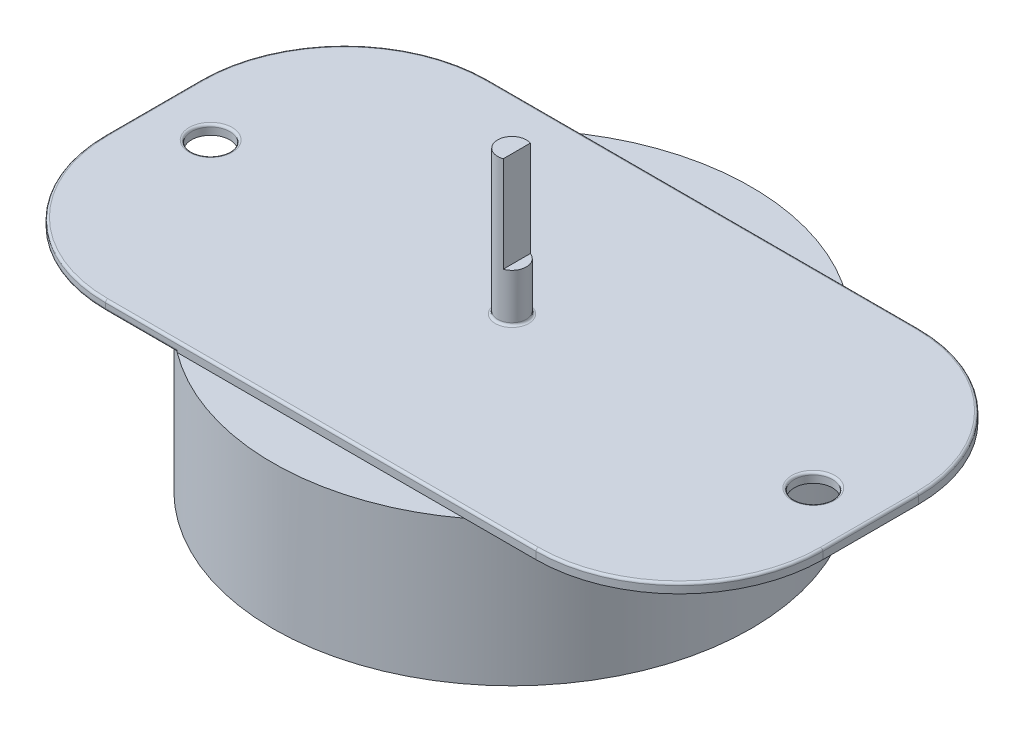
SolidWorks part; units mm, degrees
ref_plane "Plano frontal" through (0, 0, 0) normal (0, 0, 1) x (1, 0, 0)
ref_plane "Plano superior" through (0, 0, 0) normal (0, 1, 0) x (1, 0, 0)
ref_plane "Plano direito" through (0, 0, 0) normal (1, 0, 0) x (0, 0, -1)
sketch "Esboço1" plane through (0, 0, 0) normal (0, 1, 0) x (1, 0, 0)
  circle A0 centre (0, 0) radius 50
extrude "Ressalto-extrusão1" add sketch "Esboço1" along normal blind 30
sketch "Esboço2" plane through (0, 30, 0) normal (0, 1, 0) x (1, 0, 0)
  line L1 (-45, -40) -> (45, -40)
  line L2 (-75, -10) -> (-75, 10)
  line L3 (-45, 40) -> (45, 40)
  line L4 (75, -10) -> (75, 10)
  line L5 (-75, -40) -> (75, 40) construction
  line L6 (-75, 40) -> (75, -40) construction
  arc A0 (45, 40) -> (75, 10) centre (45, 10) cw
  arc A1 (45, -40) -> (75, -10) centre (45, -10) ccw
  arc A2 (-45, -40) -> (-75, -10) centre (-45, -10) cw
  arc A3 (-75, 10) -> (-45, 40) centre (-45, 10) cw
  point P0 (0, 0)
  dimension "D3" = 30
  dimension "D1" = 150
  dimension "D2" = 80
extrude "Ressalto-extrusão2" add sketch "Esboço2" along normal blind 2
sketch "Esboço3" plane through (0, 32, 0) normal (0, 1, 0) x (1, 0, 0)
  circle A0 centre (0, 0) radius 3
  dimension "D1" = 6
extrude "Ressalto-extrusão3" add sketch "Esboço3" along normal blind 30
sketch "Esboço4" plane through (0, 62, 0) normal (0, 1, 0) x (1, 0, 0)
  line L1 (1, -3.3934) -> (3.9135, -3.3934)
  line L2 (1, -3.3934) -> (1, 3.3718)
  line L3 (1, 3.3718) -> (3.9135, 3.3718)
  line L4 (3.9135, -3.3934) -> (3.9135, 3.3718)
  dimension "D1" = 1
extrude "Corte-extrusão1" cut sketch "Esboço4" against normal blind 20
sketch "Esboço6" plane through (0, 32, 0) normal (0, 1, 0) x (1, 0, 0)
  line L0 (-75, 10) -> (-75, -10) construction
  line L1 (0, -17.6) -> (0, 17.6) construction
  circle A0 centre (-63, 0) radius 4
  circle A1 centre (63, 0) radius 4
  dimension "D1" = 12
extrude "Corte-extrusão2" cut sketch "Esboço6" against normal up to next
fillet "Filete2" radius 0.5 16 edges at (-37.5, 30, -40) (-37.5, 30, 40) (-66.2132, 30, 31.2132) (-75, 30, 0) (75, 32, 0) (66.2132, 32, 31.2132) (0, 32, 40) (-66.2132, 32, 31.2132) (-75, 32, 0) (-66.2132, 32, -31.2132) (0, 32, -40) (66.2132, 32, -31.2132) (0, 32, -3) (63, 32, -4) (-63, 32, 4) (-66.2132, 30, -31.2132)
